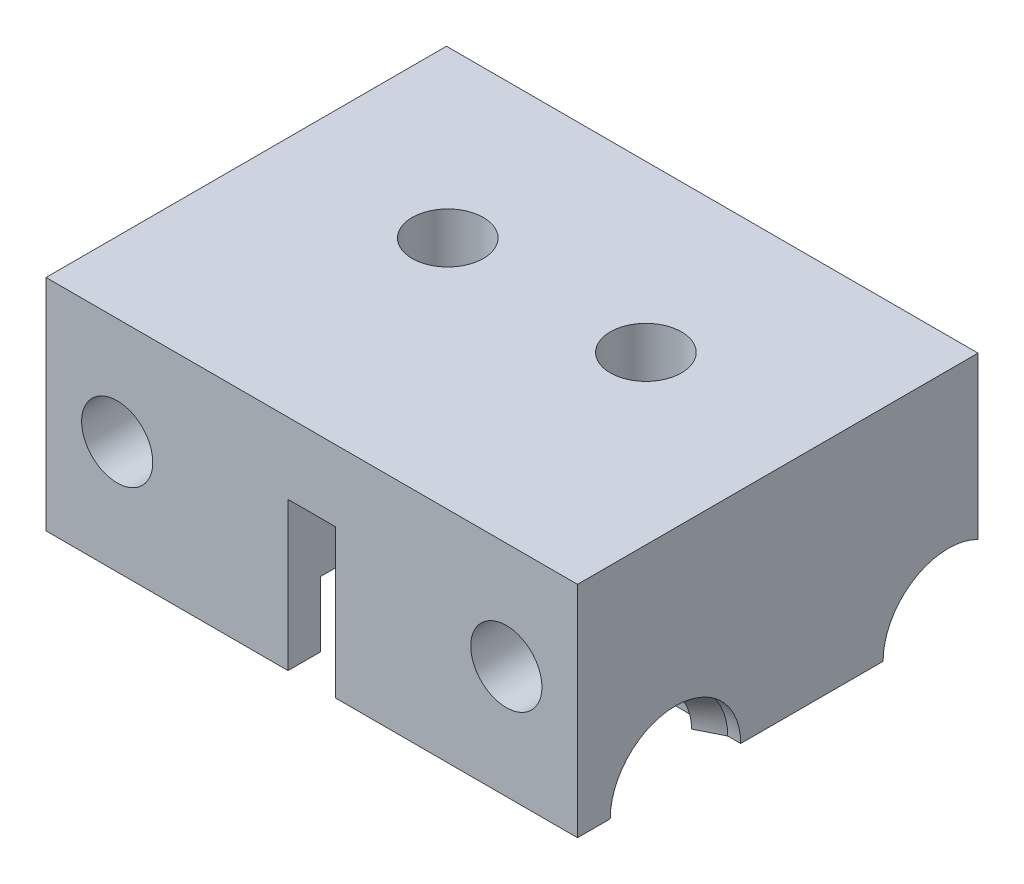
SolidWorks part; units mm, degrees
ref_plane "Front Plane" through (0, 0, 0) normal (0, 0, 1) x (1, 0, 0)
ref_plane "Top Plane" through (0, 0, 0) normal (0, 1, 0) x (1, 0, 0)
ref_plane "Right Plane" through (0, 0, 0) normal (1, 0, 0) x (0, 0, -1)
sketch "Sketch6" plane through (0, 0, 0) normal (0, 1, 0) x (1, 0, 0)
  line L0 (0, 0) -> (0, 5)
  line L1 (0, 5) -> (12.7, 5)
  line L2 (12.7, 5) -> (12.7, 2.75)
  line L6 (12.7, 2.75) -> (9.652, 2.75)
  line L7 (9.652, 2.75) -> (8.636, 2.242)
  line L8 (8.636, 2.242) -> (8.636, 2.75)
  line L9 (8.636, 2.75) -> (4.826, 2.75)
  line L10 (4.826, 2.75) -> (3.81, 2.242)
  line L11 (3.81, 2.242) -> (3.81, 2.75)
  line L12 (3.81, 2.75) -> (0, 2.75)
  line L18 (0, 0) -> (15, 0)
  dimension "D1" = 0.508
  dimension "D2" = 12.7
  dimension "D3" = 3.048
  dimension "D4" = 5
  dimension "D5" = 2.25
  dimension "D6" = 2.25
  dimension "D7" = 2.25
  dimension "D10" = 1.016
  dimension "D11" = 1.016
  dimension "D12" = 3.81
  dimension "D13" = 3.81
  dimension "D20" = 15
revolve "Revolve1" add sketch "Sketch6" angle 180 about L18 region at (6.3538, 0, -3.852)
sketch "Sketch9" plane through (0, 0, 0) normal (0, 0, 1) x (1, 0, 0)
  line L0 (0, 0) -> (0, 3.25)
  line L1 (0, 3.25) -> (0, 5)
  line L2 (0, 5) -> (12.7, 5)
  line L3 (12.7, 5) -> (12.7, 2.75)
  line L4 (12.7, 2.75) -> (12.7, 0)
  line L5 (12.7, 0) -> (0, 0)
  line L6 (0, 3.25) -> (12.7, 2.75)
  dimension "D1" = 3.25
extrude "Boss-Extrude1" add sketch "Sketch9" along normal blind 9.25 and the other way blind 9.25 contours L1 L6 L3 L2 region at (6.6146, 3.9948, 0)
extrude "Boss-Extrude2" add sketch "Sketch9<3>" along normal blind 5.75 from offset 3.5 contours L6 L0 L5 L4 region at (6.1736, 1.5035, 0)
sketch "Sketch9<3>" plane through (0, 0, 0) normal (0, 0, 1) x (1, 0, 0) same geometry as "Sketch9"
extrude "Boss-Extrude3" add sketch "Sketch9<4>" against normal blind 5.75 from offset 3.5 contours L6 L0 L5 L4 region at (6.1736, 1.5035, 0) offset against normal yes
sketch "Sketch9<4>" plane through (0, 0, 0) normal (0, 0, 1) x (1, 0, 0) same geometry as "Sketch9"
sketch "Sketch14" plane through (0, 0, 0) normal (-1, 0, 0) x (0, 0, 1)
  line L0 (-9.25, 5) -> (9.25, 5) construction
  line L1 (-9.25, 0) -> (-6.75, 0)
  line L2 (-9.25, 0) -> (-9.25, 5)
  line L3 (-9.25, 5) -> (-6.75, 5)
  line L4 (-6.75, 0) -> (-6.75, 5)
  dimension "D1" = 2.5
extrude "Cut-Extrude10" cut sketch "Sketch14" against normal through all
ref_plane "Plane3" through (0, 0, -5.75) normal (0, 0, 1) x (1, 0, 0)
mirror "Mirror4" about plane through (0, 0, -5.75) normal (0, 0, 1) of bodies 150 146
sketch "Sketch13" plane through (0, 0, 0) normal (-1, 0, 0) x (0, 0, 1)
  line L0 (-2.75, 0) -> (-8.75, 0) construction
  line L1 (-2.75, 0) -> (2.75, 0)
  line L2 (-2.75, 0) -> (-2.75, 2.75)
  line L3 (-2.75, 2.75) -> (2.75, 2.75)
  line L4 (2.75, 0) -> (2.75, 2.75)
  point P6 (0, 0)
  dimension "D1" = 5.5
  dimension "D2" = 2.75
extrude "Cut-Extrude9" cut sketch "Sketch13" against normal blind 1.75
sketch "Sketch15" plane through (0, 5, 0) normal (0, 1, 0) x (1, 0, 0)
  line L0 (0, 20.75) -> (0, -9.25) construction
  line L1 (12.7, 20.75) -> (0, 20.75)
  line L2 (12.7, 20.75) -> (12.7, 12.75)
  line L3 (12.7, 12.75) -> (0, 12.75)
  line L4 (0, 20.75) -> (0, 12.75)
  dimension "D1" = 8
extrude "Cut-Extrude11" cut sketch "Sketch15" against normal through all
sketch "Sketch16" plane through (0, 0, 0) normal (-1, 0, 0) x (0, 0, 1)
  line L0 (-12.75, 5) -> (9.25, 5) construction
  line L1 (9.25, 0) -> (4.1274, 0)
  line L2 (9.25, 0) -> (9.25, 5)
  line L3 (9.25, 5) -> (4.1274, 5)
  line L4 (4.1274, 0) -> (4.1274, 5)
extrude "Cut-Extrude12" cut sketch "Sketch16" against normal through all
sketch "Sketch22" plane through (0, 0, 4.1274) normal (0, 0, 1) x (1, 0, 0)
  line L0 (12.7, 0) -> (0, 0) construction
  line L1 (12.7, 5) -> (10.2, 5)
  line L2 (12.7, 5) -> (12.7, 0)
  line L3 (12.7, 0) -> (10.2, 0)
  line L4 (10.2, 5) -> (10.2, 0)
  dimension "D1" = 2.5
extrude "Cut-Extrude17" cut sketch "Sketch22" against normal through all
ref_plane "Plane5" through (0, 0, 5.3974) normal (0, 0, 1) x (1, 0, 0)
mirror "Mirror8" about plane through (0, 0, 5.3974) normal (0, 0, 1) of bodies 160 152
sketch "Sketch17" plane through (0, 5, 0) normal (0, 1, 0) x (1, 0, 0)
  line L1 (0, -4.1274) -> (10.2, -4.1274)
  line L2 (0, -4.1274) -> (0, 12.75)
  line L3 (0, 12.75) -> (10.2, 12.75)
  line L4 (10.2, -4.1274) -> (10.2, 12.75)
extrude "Boss-Extrude4" add sketch "Sketch17" along normal blind 4.25
sketch "Sketch18" plane through (0, 9.25, 0) normal (0, 1, 0) x (1, 0, 0)
  line L0 (10.2, -4.1274) -> (10.2, 12.75) construction
  line L1 (0, 12.75) -> (0, -4.1274) construction
  line L2 (0, -4.1274) -> (10.2, -4.1274) construction
  circle A0 centre (3.175, 5.7786) radius 1.5
  circle A1 centre (7.025, 5.7786) radius 1.5
  dimension "D1" = 3
  dimension "D2" = 3
  dimension "D3" = 3.175
  dimension "D4" = 3.175
  dimension "D5" = 9.906
extrude "Cut-Extrude13" cut sketch "Sketch18" against normal through all contours A0 region at (3.175, 9.25, -5.7786)
sketch "Sketch19" plane through (0, 5, 0) normal (0, 1, 0) x (1, 0, 0)
  line L0 (0, -23.5447) -> (0, -6.6674) construction
  line L2 (10.2, -6.6674) -> (0, -6.6674) construction
  circle A0 centre (3.175, -16.5734) radius 1.5
  dimension "D4" = 3
  dimension "D1" = 3.175
  dimension "D5" = 9.906
extrude "Cut-Extrude14" cut sketch "Sketch19" against normal through all
sketch "Sketch20" plane through (0, 0, 4.1274) normal (0, 0, 1) x (1, 0, 0)
  line L0 (10.2, 9.25) -> (10.2, 0) construction
  line L1 (0, 9.25) -> (10.2, 9.25) construction
  circle A0 centre (7.2, 4.75) radius 1.5
  dimension "D1" = 3
  dimension "D2" = 3
  dimension "D3" = 4.5
extrude "Cut-Extrude16" cut sketch "Sketch20" against normal through all
sketch "Sketch23" plane through (0, 0, 0) normal (-1, 0, 0) x (0, 0, 1)
  line L0 (4.1274, 9.25) -> (4.1274, 0) construction
  line L1 (-12.75, 9.25) -> (4.1274, 9.25)
  line L2 (-12.75, 9.25) -> (-12.75, 6.25)
  line L3 (-12.75, 6.25) -> (4.1274, 6.25)
  line L4 (4.1274, 9.25) -> (4.1274, 6.25)
  dimension "D1" = 3
extrude "Boss-Extrude5" add sketch "Sketch23" along normal blind 1
ref_plane "Plane6" through (-1, 0, 0) normal (-1, 0, 0) x (0, 0, 1)
mirror "Mirror9" about plane through (-1, 0, 0) normal (-1, 0, 0) of bodies 162 159
delete or keep bodies "Body-Delete/Keep 1" type delete bodies bodies 157
combine bodies "Combine1" operation type add bodies to combine 161 162
